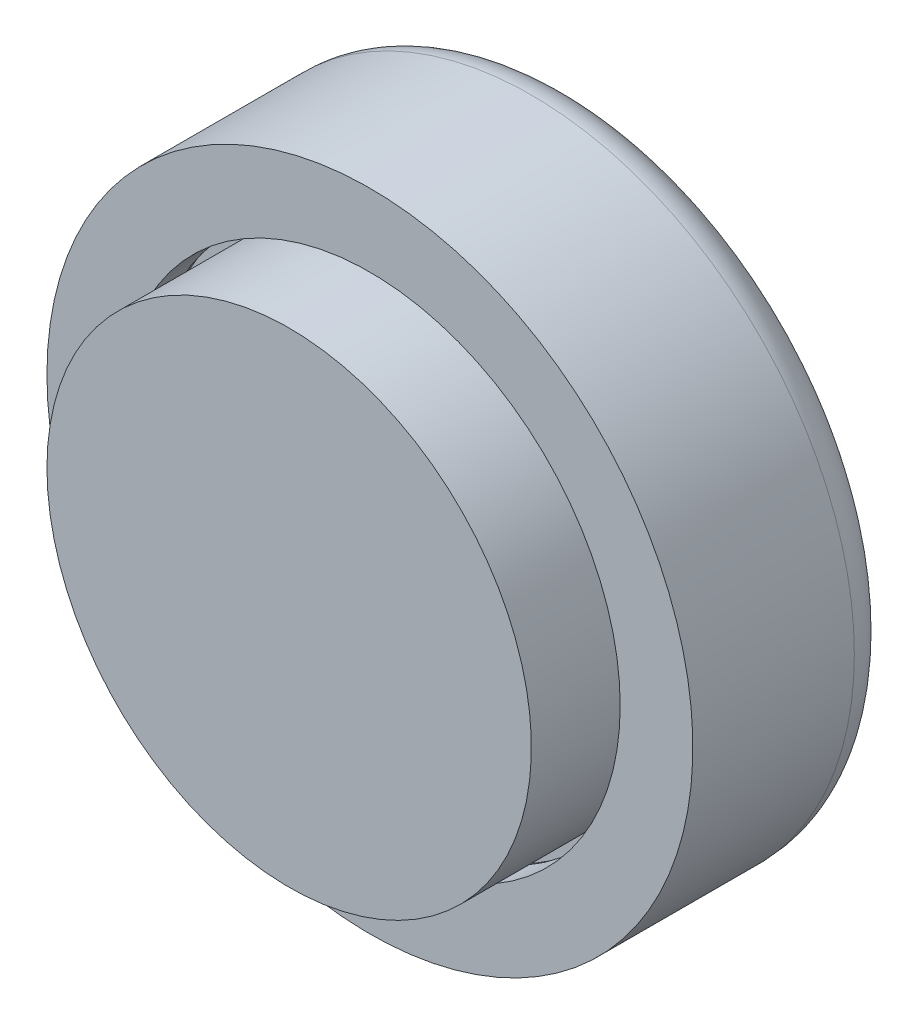
SolidWorks part; units mm, degrees
other "btm"
other "cap"
ref_plane "Front Plane" through (0, 0, 0) normal (0, 0, 1) x (1, 0, 0)
ref_plane "Top Plane" through (0, 0, 0) normal (0, 1, 0) x (1, 0, 0)
ref_plane "Right Plane" through (0, 0, 0) normal (1, 0, 0) x (0, 0, -1)
sketch "Sketch3" plane through (0, 0, 0) normal (0, 1, 0) x (1, 0, 0)
  line L0 (0, 0) -> (6, 0)
  line L1 (6, 0) -> (6, 3)
  line L2 (6, 3) -> (6.25, 3)
  line L3 (6.25, 3) -> (6.25, 4)
  line L4 (6.25, 4) -> (4, 4)
  line L5 (4, 4) -> (4, 1)
  line L6 (4, 1) -> (0, 1)
  line L7 (0, 1) -> (0, 0)
  line L8 (0, 0) -> (0, -5.9108) construction
  line L10 (6.45, 6) -> (6.45, 2.8)
  line L11 (6.45, 2.8) -> (6.2, 2.8)
  line L12 (6.2, 2.8) -> (6.2, 2)
  line L13 (6.2, 2) -> (8, 2)
  line L14 (8, 2) -> (8, 7)
  line L15 (8, 7) -> (0, 7)
  line L16 (0, 7) -> (0, 4)
  line L17 (3.5, 6) -> (3.5, 4)
  line L18 (3.5, 4) -> (0, 4)
  line L20 (3.5, 6) -> (6.45, 6)
  point P21 (2, 3.6011)
  point P23 (0.6231, 5.1144)
  point P24 (0, 5.436)
  point P25 (0, 0)
  dimension "D1" = 6
  dimension "D2" = 0.25
  dimension "D3" = 4
  dimension "D4" = 1
  dimension "D5" = 1
  dimension "D6" = 4
  dimension "D7" = 8
  dimension "D8" = 2
  dimension "D9" = 0.2
  dimension "D10" = 0.2
  dimension "D11" = 0.2
  dimension "D12" = 2
  dimension "D13" = 7
  dimension "D14" = 0.5
  dimension "D15" = 1
revolve "Revolve3" add sketch "Sketch3" angle 360 about L8 region at (4.0434, 0, -1.5408)
revolve "Revolve4" add sketch "Sketch3<3>" angle 360 about L8 region at (4.975, 0, -6.0943)
sketch "Sketch3<3>" plane through (0, 0, 0) normal (0, 1, 0) x (1, 0, 0) same geometry as "Sketch3"
sketch "Sketch4" plane through (0, 0, -7) normal (0, 0, -1) x (-1, 0, 0)
  line L0 (-6.5, -2) -> (6.5, -2) construction
  line L1 (0, -2) -> (0, 0) construction
  text T0 "<b>DRS</b>" font "Century Gothic" height 4
  dimension "D1" = 2
  dimension "D2" = 13
extrude "Cut-Extrude2" cut sketch "Sketch4" against normal blind 0.4
fillet "Fillet1" radius 1 1 edges at (-8, 0, -7)
sketch "Sketch5" plane through (0, 0, -6) normal (0, 0, 1) x (1, 0, 0)
  line L0 (0, -55) -> (0, 55) construction
  line L1 (-1, 3) -> (1, 3)
  line L2 (-1, 3) -> (-1, 4.5)
  line L3 (-1, 4.5) -> (1, 4.5)
  line L4 (1, 3) -> (1, 4.5)
  line L5 (0, 0) -> (0, 6.8491) construction
  circle A1 centre (0, 0) radius 3.5 construction
  circle A2 centre (0, 0) radius 3.5 construction
  point P6 (0, 4.5)
  dimension "D2" = 0.5
  dimension "D3" = 1
  dimension "D1" = 2
extrude "Boss-Extrude1" add sketch "Sketch5" along normal blind 3
sketch "Sketch6" plane through (0, 0, -4) normal (0, 0, -1) x (-1, 0, 0)
  line L0 (-1.2, 2.8) -> (1.2, 2.8)
  line L1 (1.2, 2.8) -> (1.2, 4.7)
  line L2 (1.2, 4.7) -> (-1.2, 4.7)
  line L3 (-1.2, 4.7) -> (-1.2, 2.8)
  line L4 (-1, 3) -> (1, 3)
  line L5 (-1, 4.5) -> (-1, 3)
  line L6 (1, 4.5) -> (-1, 4.5)
  line L7 (1, 3) -> (1, 4.5)
  line L8 (-1, 3) -> (1, 3) construction
  line L9 (-1, 4.5) -> (-1, 3) construction
  line L10 (1, 4.5) -> (-1, 4.5) construction
  line L11 (1, 3) -> (1, 4.5) construction
  dimension "D1" = 0
  dimension "D2" = 0.2
extrude "Cut-Extrude3" cut sketch "Sketch6" against normal up to surface (3 mm away) up to face at (-4, 0, -1)
